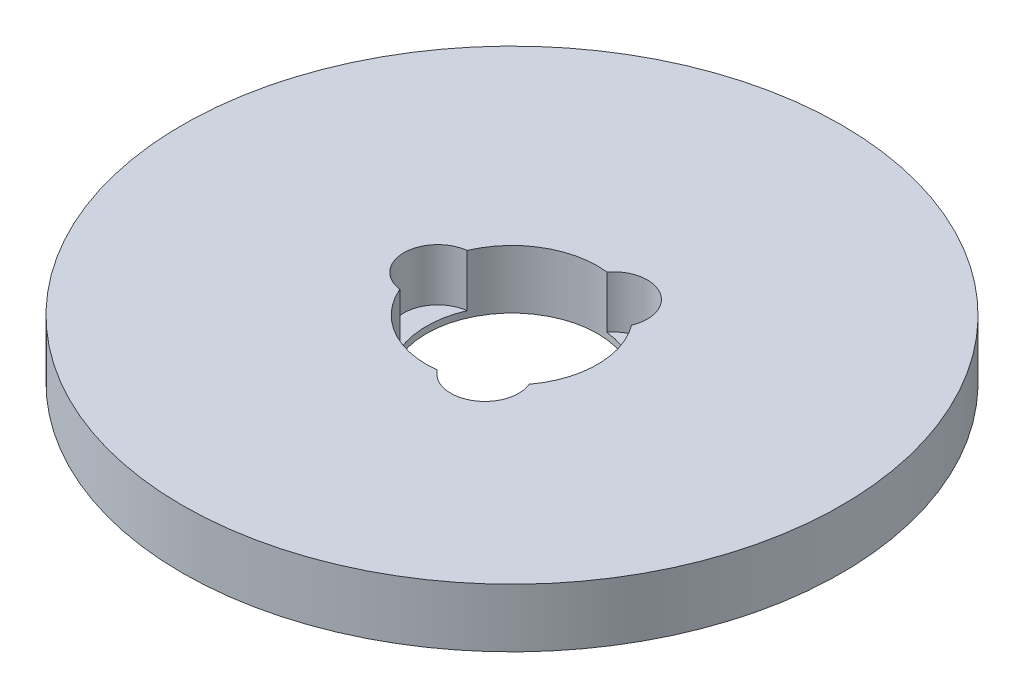
SolidWorks part; units mm, degrees
ref_plane "Front Plane" through (0, 0, 0) normal (0, 0, 1) x (1, 0, 0)
ref_plane "Top Plane" through (0, 0, 0) normal (0, 1, 0) x (1, 0, 0)
ref_plane "Right Plane" through (0, 0, 0) normal (1, 0, 0) x (0, 0, -1)
sketch "Sketch1" plane through (0, 0, 0) normal (0, 1, 0) x (1, 0, 0)
  circle A0 centre (0, 0) radius 67.5
  dimension "FLANGE_OD" = 135
extrude "Boss-Extrude1" add sketch "Sketch1" along normal blind 12
sketch "Sketch2" plane through (0, 0, 0) normal (0, 1, 0) x (1, 0, 0)
  circle A0 centre (0, 0) radius 17.5
  dimension "BORE_D" = 35
extrude "Cut-Extrude1" cut sketch "Sketch2" along normal through all
sketch "Sketch3" plane through (0, 12, 0) normal (0, 1, 0) x (1, 0, 0)
  circle A0 centre (0, 0) radius 15.2054 construction
  circle A1 centre (-15.2054, 0) radius 6.9545
  dimension "BOLT_D" = 13.909
  dimension "BOLT_PCD" = 30.4109
extrude "Cut-Extrude2" cut sketch "Sketch3" against normal blind 10.6873
pattern_circular "CirPattern1" count 3 over 360 about axis through (0, 0, 0) along (0, 1, 0) of "Cut-Extrude2"
